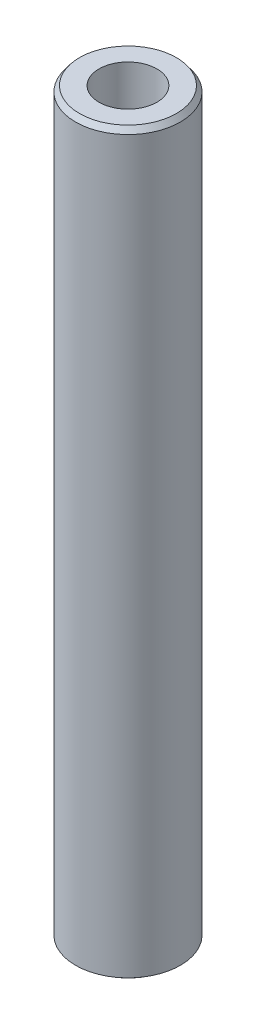
SolidWorks part; units mm, degrees
ref_plane "Front Plane" through (0, 0, 0) normal (0, 0, 1) x (1, 0, 0)
ref_plane "Top Plane" through (0, 0, 0) normal (0, 1, 0) x (1, 0, 0)
ref_plane "Right Plane" through (0, 0, 0) normal (1, 0, 0) x (0, 0, -1)
sketch "Sketch1" plane through (0, 0, 0) normal (0, 1, 0) x (1, 0, 0)
  circle A0 centre (0, 0) radius 42.5
  dimension "SHAFT_OD" = 85
extrude "Boss-Extrude1" add sketch "Sketch1" along normal blind 600
sketch "Sketch2" plane through (0, 0, 0) normal (0, 1, 0) x (1, 0, 0)
  circle A0 centre (0, 0) radius 23.4739
  dimension "BORE_D" = 46.9478
extrude "Cut-Extrude1" cut sketch "Sketch2" along normal through all
chamfer "Chamfer1" distance 4.39 angle 36.012 2 edges at (0, 600, 42.5) (0, 0, 42.5) first distance on face at (0, 600, 42.5) first distance on face at (0, 0, 23.4739)
